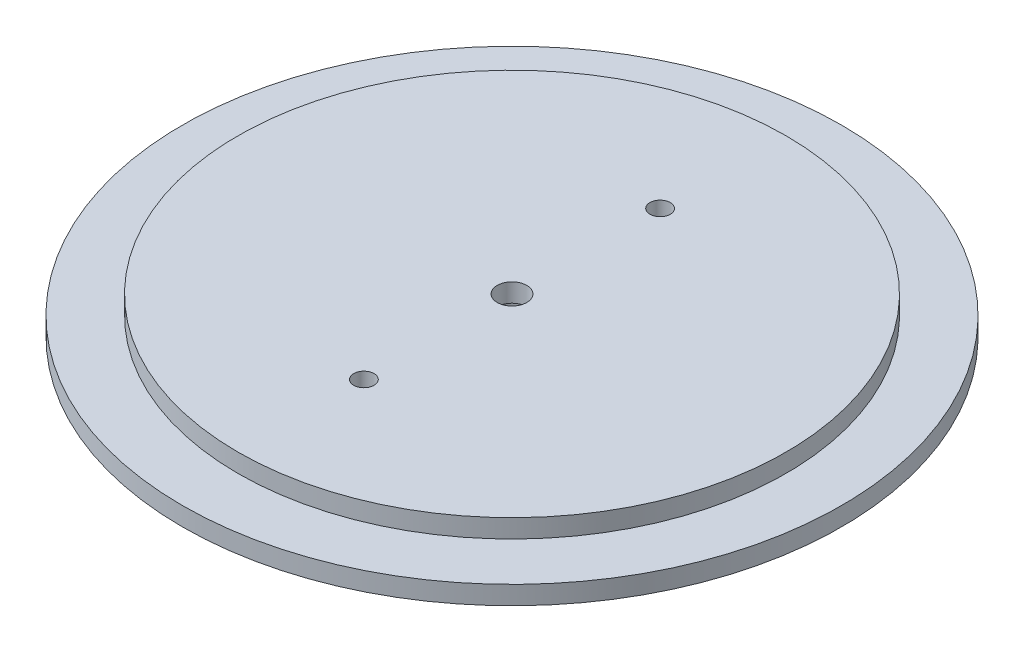
SolidWorks part; units mm, degrees
ref_plane "Front Plane" through (0, 0, 0) normal (0, 0, 1) x (1, 0, 0)
ref_plane "Top Plane" through (0, 0, 0) normal (0, 1, 0) x (1, 0, 0)
ref_plane "Right Plane" through (0, 0, 0) normal (1, 0, 0) x (0, 0, -1)
sketch "Sketch1" plane through (0, 0, 0) normal (0, 1, 0) x (1, 0, 0)
  circle A0 centre (0, 0) radius 89
  dimension "D1" = 178
extrude "Boss-Extrude1" add sketch "Sketch1" along normal blind 5
sketch "Sketch2" plane through (0, 5, 0) normal (0, 1, 0) x (1, 0, 0)
  circle A0 centre (0, 0) radius 74
  dimension "D1" = 148
extrude "Boss-Extrude2" add sketch "Sketch2" along normal blind 5
sketch "Sketch3" plane through (0, 10, 0) normal (0, 1, 0) x (1, 0, 0)
  line L0 (0, 0) -> (0, 40) construction
  line L1 (0, 0) -> (0, -40) construction
  circle A0 centre (0, 40) radius 2.75
  circle A1 centre (0, -40) radius 2.75
  dimension "D3" = 5.5
  dimension "D4" = 5.5
  dimension "D1" = 40
  dimension "D2" = 40
extrude "Cut-Extrude1" cut sketch "Sketch3" against normal blind 10
sketch "Sketch4" plane through (0, 10, 0) normal (0, 1, 0) x (1, 0, 0)
  circle A0 centre (0, 0) radius 4
  dimension "D1" = 8
extrude "Cut-Extrude2" cut sketch "Sketch4" against normal blind 5
sketch "Sketch5" plane through (0, 0, 0) normal (0, -1, 0) x (1, 0, 0)
  circle A0 centre (0, 0) radius 6
  dimension "D1" = 12
extrude "Cut-Extrude3" cut sketch "Sketch5" against normal blind 5
